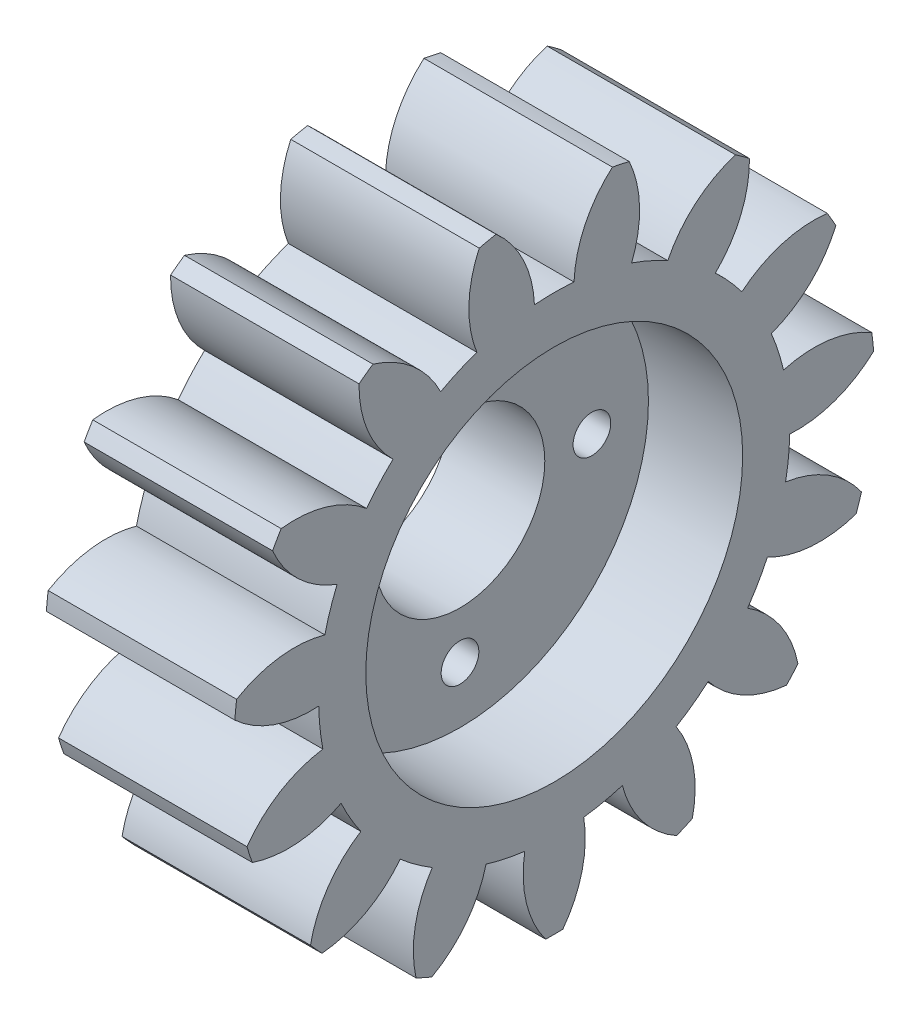
SolidWorks part; units mm, degrees
material "ABS"
ref_plane "Plane1" through (0, 0, 0) normal (0, 0, 1) x (1, 0, 0)
ref_plane "Plane2" through (0, 0, 0) normal (0, 1, 0) x (1, 0, 0)
ref_plane "Plane3" through (0, 0, 0) normal (1, 0, 0) x (0, 0, -1)
other "Configuration Table"
sketch "HoldingSke" plane through (0, 0, 0) normal (0, 1, 0) x (1, 0, 0)
  line L0 (0, 0) -> (0.483, -0.1294)
  line L1 (-15, 0) -> (100, 0) construction
  line L2 (0, 0) -> (-2.1039, 2.3779)
  line L3 (0, 0) -> (-11.863, 4.5341)
  line L4 (0, 0) -> (8.3417, 2.2352)
  line L5 (0, 0) -> (-46.8476, -17.4728)
  line L6 (0, 0) -> (-8.2896, -5.593)
  line L7 (-2.1039, 2.3779) -> (8.6586, 51.2059)
  line L8 (-76.2, 54.61) -> (-73.4, 54.61)
  line L9 (-71.009, 38.7566) -> (-53.1078, 45.2721)
  line L10 (-76.2, 71.12) -> (104.1128, 71.12)
  line L11 (0, 0) -> (-10, 0)
  line L12 (-76.2, 101.6) -> (-76.133, 101.6)
  line L13 (24.9733, 27.94) -> (52.9518, 28.4284)
  line L14 (24.9733, 27.94) -> (24.9743, 27.94)
  line L15 (24.9733, 27.94) -> (100.4006, 29.5858)
  line L16 (-63.627, -2) -> (-12.827, -2)
  circle A0 centre (0, 0) radius 10
  circle A1 centre (0, 0) radius 12.499
  circle A2 centre (0, 0) radius 37.5
  circle A3 centre (0, 0) radius 10
  dimension "Num_teeth" = 15
  dimension "Pitch_radius" = 180.3128
  dimension "Width" = 10
  dimension "Thickness" = 10
sketch "BasProSke" plane through (0, 0, 0) normal (0, 1, 0) x (1, 0, 0)
  line L0 (-10, 0) -> (60, 0) construction
  line L1 (0, 0) -> (0, 17)
  line L2 (0, 0) -> (10, 0)
  line L3 (10, 0) -> (10, 17)
  line L4 (10, 17) -> (0, 17)
  dimension "Thickness" = 10
  dimension "Diameter" = 34
revolve "Base-Revolve" add sketch "BasProSke" angle 360 about L0
sketch "TooCutSke" plane through (0, 0, 0) normal (1, 0, 0) x (0, 0, -1)
  line L1 (0, 0) -> (0, 107) construction
  line L2 (0, 0) -> (-1.6851, 14.905) construction
  line L3 (0, 0) -> (-6.2081, 29.2069) construction
  line L4 (-1.6851, 14.905) -> (-3.1041, 14.6034) construction
  arc A0 (1.0501, 12.4548) -> (-1.0501, 12.4548) centre (0, 0) ccw
  arc A1 (3.1109, 16.7388) -> (-3.1109, 16.7388) centre (0, 0) ccw
  circle A2 centre (0, 0) radius 15 construction
  circle A3 centre (0, 0) radius 14.0954 construction
  arc A4 (-1.0501, 12.4548) -> (-3.1109, 16.7388) centre (-7.045, 12.2085) ccw
  arc A5 (3.1109, 16.7388) -> (1.0501, 12.4548) centre (7.045, 12.2085) ccw
extrude "ToothCut" cut sketch "TooCutSke" along normal through all
fillet "Breaks" [suppressed] radius 0.04 tangent propagation no
fillet "RootFillets" [suppressed] radius 0.501
pattern_circular "TeethCuts" count 15 every 24 about axis through (-10, 0, 0) along (1, 0, 0) of "ToothCut", "RootFillets", "Breaks"
sketch "HubNeaOneSke" plane through (0, 0, 0) normal (-1, 0, 0) x (0, 0, 1)
  circle A0 centre (0, 0) radius 12.499
  dimension "Diameter" = 24.998
extrude "HubNearOne" [suppressed] add sketch "HubNeaOneSke" along normal blind 40.0001
sketch "HubNeaBotSke" plane through (0, 0, 0) normal (-1, 0, 0) x (0, 0, 1)
  circle A0 centre (0, 0) radius 12.499
  dimension "Diameter" = 24.998
extrude "HubNearBoth" [suppressed] add sketch "HubNeaBotSke" along normal blind 20
ref_plane "FarPln" through (10, 0, 0) normal (1, 0, 0) x (0, 0, -1)
sketch "HubFarSke" plane through (10, 0, 0) normal (1, 0, 0) x (0, 0, -1)
  circle A0 centre (0, 0) radius 12.499
  dimension "Diameter" = 24.998
extrude "HubFar" [suppressed] add sketch "HubFarSke" along normal blind 20
sketch "BorSke" plane through (0, 0, 0) normal (1, 0, 0) x (0, 0, -1)
  circle A0 centre (0, 0) radius 10
  dimension "Diameter" = 20
extrude "Bore" cut sketch "BorSke" along normal mid plane 100.0001
sketch "KeySke" plane through (0, 0, 0) normal (1, 0, 0) x (0, 0, -1)
  line L0 (-3, 0) -> (-3, 12.8)
  line L1 (-3, 12.8) -> (3, 12.8)
  line L2 (3, 12.8) -> (3, 0)
  line L3 (0, 0) -> (0, 34) construction
  line L4 (-3, 0) -> (3, 0)
  dimension "Width" = 6
extrude "Keyway" [suppressed] cut sketch "KeySke" along normal mid plane 100.0001
pattern_circular "Keyway2" [suppressed] count 2 every 90 about axis through (-10, 0, 0) along (1, 0, 0)
sketch "Sketch1" plane through (0, 0, 0) normal (1, 0, 0) x (0, 0, -1)
  circle A0 centre (0, 0) radius 10 construction
  circle A1 centre (0, 0) radius 10
  circle A2 centre (7, 0) radius 1
  circle A3 centre (-7, 0) radius 1
  circle A4 centre (0, 0) radius 7 construction
  circle A5 centre (0, 7) radius 1
  circle A6 centre (0, -7) radius 1
  circle A7 centre (0, 0) radius 4.5
  dimension "D1" = 2
  dimension "D2" = 14
  dimension "D3" = 9
extrude "Boss-Extrude1" add sketch "Sketch1" along normal blind 5
equation "' \"Module@HoldingSke\" = 6.35"
equation "' \"Num_teeth@HoldingSke\" = 12"
equation "' \"Ap@HoldingSke\" =  20"
equation "' \"Ap@HoldingSke\" = 20"
equation "' \"Width@HoldingSke\" = 0.5 * 25.4"
equation "' \"Hub_dia@HoldingSke\"= 1 * 25.4"
equation "' \"Hub_dia@HoldingSke\" = 1 * 25.4"
equation "' \"Overall_len@HoldingSke\" = 1.0 * 25.4"
equation "' \"Bore@HoldingSke\" = 0.75 * 25.4"
equation "' \"T_dim@HoldingSke\" = 0.1 * 25.4"
equation "' \"Width@KeySke\" = 0.25 * 25.4"
equation "' \"Show_teeth@HoldingSke\" = 13"
equation "' \"Backlash@HoldingSke\" = 0.009 * 25.4"
equation "' \"Addendum_fac@HoldingSke\" = 1.0"
equation "' \"Dedendum_fac@HoldingSke\" = 1.25"
equation "' \"Dedendum_add@HoldingSke\" = 0.00005 * 25.4"
equation "' \"Clearance_fac@HoldingSke\" = 0.25"
equation "\"Pitch@HoldingSke\" = 1 / \"Module@HoldingSke\""
equation "\"Overcut_dia@TooCutSke\" = (\"Num_teeth@HoldingSke\" + 2 * \"Addendum_fac@HoldingSke\") / \"Pitch@HoldingSke\" + 0.002 * 25.4"
equation "\"Pitch_dia@TooCutSke\" = \"Num_teeth@HoldingSke\" / \"Pitch@HoldingSke\""
equation "\"Base_dia@TooCutSke\" = \"Num_teeth@HoldingSke\" / \"Pitch@HoldingSke\" * cos((\"Ap@HoldingSke\"  * 3.14159265 / 180))"
equation "\"Root_dia@TooCutSke\" = (\"Num_teeth@HoldingSke\" + 2) / \"Pitch@HoldingSke\" - 2 * (\"Addendum_fac@HoldingSke\" + \"Dedendum_fac@HoldingSke\") / \"Pitch@HoldingSke\" - \"Dedendum_add@HoldingSke\" * 2"
equation "\"Half_ang@TooCutSke\" = 180 / \"Num_teeth@HoldingSke\""
equation "\"Half_CT@TooCutSke\" = \"Num_teeth@HoldingSke\" / \"Pitch@HoldingSke\" * sin((3.14159265 / 2 / \"Num_teeth@HoldingSke\")) / 2 - 7 * \"Backlash@HoldingSke\" / 4"
equation "\"Flank_rad@TooCutSke\" = \"Num_teeth@HoldingSke\" / \"Pitch@HoldingSke\" / 5"
equation "\"Radius@RootFillets\" = \"Clearance_fac@HoldingSke\" / \"Pitch@HoldingSke\" + \"Dedendum_add@HoldingSke\""
equation "\"Break_rad@Breaks\" = 0.02 / \"Pitch@HoldingSke\""
equation "\"Thickness@HoldingSke\" = \"Width@HoldingSke\""
equation "\"OAL@HoldingSke\" = \"Thickness@HoldingSke\""
equation "\"MHD@HoldingSke\" = (\"Num_teeth@HoldingSke\" + 2) / \"Pitch@HoldingSke\" - 2 * (\"Addendum_fac@HoldingSke\" + \"Dedendum_fac@HoldingSke\")  / \"Pitch@HoldingSke\" - \"Dedendum_add@HoldingSke\" * 2"
equation "\"MBD@HoldingSke\" = (\"Num_teeth@HoldingSke\" + 2) / \"Pitch@HoldingSke\" - 2 * (\"Addendum_fac@HoldingSke\" + \"Dedendum_fac@HoldingSke\")  / \"Pitch@HoldingSke\" - \"Dedendum_add@HoldingSke\" * 2 - 0.002 * 25.4"
equation "\"MHD@HoldingSke\" = ((sgn( \"MHD@HoldingSke\" - \"Hub_dia@HoldingSke\" )-1)*( \"MHD@HoldingSke\" - \"Hub_dia@HoldingSke\" ))/-2+ \"Hub_dia@HoldingSke\""
equation "\"MBD@HoldingSke\" = ((sgn( \"MBD@HoldingSke\" - \"Bore@HoldingSke\" )-1)*( \"MBD@HoldingSke\" - \"Bore@HoldingSke\" ))/-2+ \"Bore@HoldingSke\""
equation "\"OAL@HoldingSke\" = ((sgn( \"OAL@HoldingSke\" - \"Overall_len@HoldingSke\" )+1)*( \"OAL@HoldingSke\" - \"Overall_len@HoldingSke\" ))/2 + \"Overall_len@HoldingSke\" + 0.000002 * 25.4"
equation "\"Num_teeth@TeethCuts\" = int( \"Show_teeth@HoldingSke\" ) + 1"
equation "\"Num_teeth@TeethCuts\" = ((sgn( \"Num_teeth@TeethCuts\" - \"Num_teeth@HoldingSke\" )-1)*( \"Num_teeth@TeethCuts\" - \"Num_teeth@HoldingSke\" ))/-2+ \"Num_teeth@HoldingSke\""
equation "\"Num_teeth@TeethCuts\" = ((sgn( \"Num_teeth@TeethCuts\" - 2.0)+1)*( \"Num_teeth@TeethCuts\" - 2.0))/2 +2.0"
equation "\"Angle@TeethCuts\" = 360.0 / \"Num_teeth@HoldingSke\""
equation "\"Diameter@BasProSke\" = (\"Num_teeth@HoldingSke\" + 2 * \"Addendum_fac@HoldingSke\") / \"Pitch@HoldingSke\""
equation "\"Thickness@BasProSke\"  = \"Thickness@HoldingSke\""
equation "' \"Fillet_rad@BasProSke\" =  \"Thickness@HoldingSke\" * 0.05"
equation "' \"Fillet_rad@BasProSke\" = \"Thickness@HoldingSke\" * 0.05"
equation "\"MHD@HoldingSke\" = ((sgn( \"MHD@HoldingSke\" - \"Root_dia@TooCutSke\" )-1)*( \"MHD@HoldingSke\" - \"Root_dia@TooCutSke\" ))/-2+ \"Root_dia@TooCutSke\""
equation "\"Diameter@HubNeaOneSke\" = \"MHD@HoldingSke\""
equation "\"Length@HubNearOne\" = \"OAL@HoldingSke\" - \"Thickness@BasProSke\""
equation "\"Diameter@HubNeaBotSke\" = \"MHD@HoldingSke\""
equation "\"Length@HubNearBoth\" = ( \"OAL@HoldingSke\" - \"Thickness@BasProSke\" ) / 2.0"
equation "\"Thickness@FarPln\" = \"Thickness@BasProSke\""
equation "\"Diameter@HubFarSke\" = \"MHD@HoldingSke\""
equation "\"Length@HubFar\" = ( \"OAL@HoldingSke\" - \"Thickness@BasProSke\" ) / 2.0"
equation "\"Diameter@BorSke\" = \"MBD@HoldingSke\""
equation "\"D1@Bore\" = \"OAL@HoldingSke\" * 2.0"
equation "\"D1@Keyway\" = \"OAL@HoldingSke\" * 2.0"
equation "\"Offset@KeySke\" = \"T_dim@HoldingSke\" + \"MBD@HoldingSke\" / 2.0"
